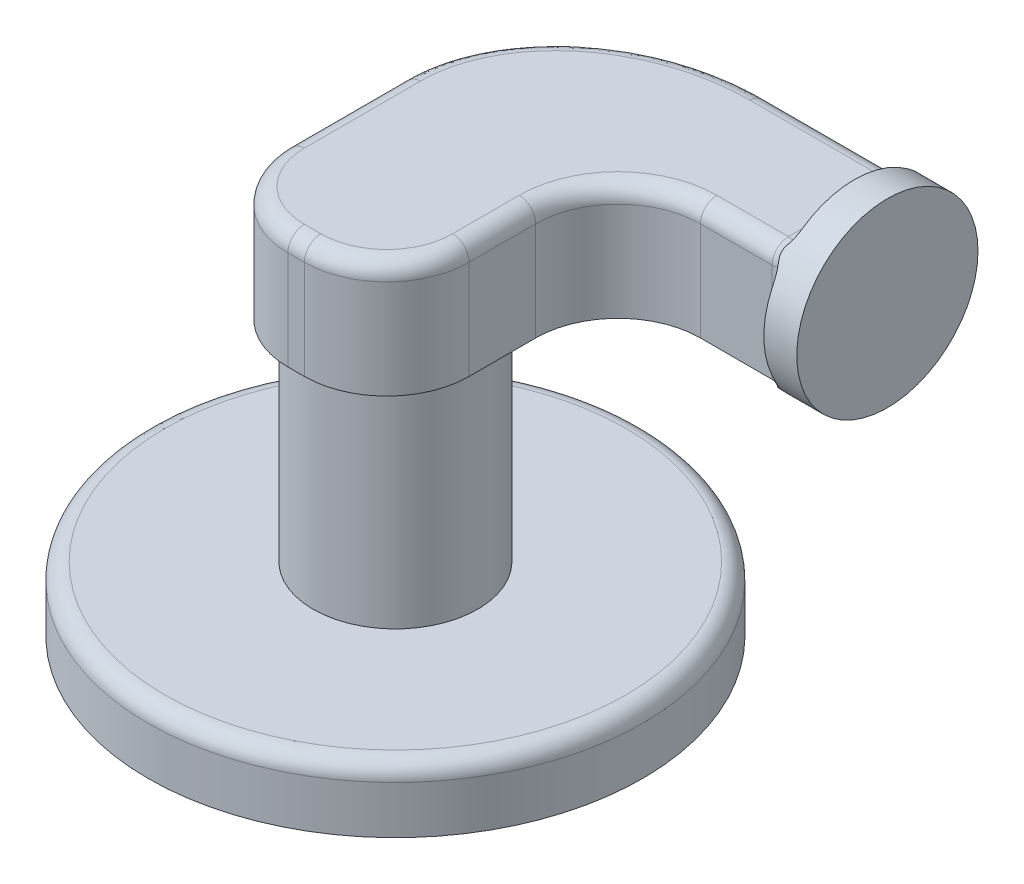
SolidWorks part; units mm, degrees
material "AISI 1020"
ref_plane "Front Plane" through (0, 0, 0) normal (0, 0, 1) x (1, 0, 0)
ref_plane "Top Plane" through (0, 0, 0) normal (0, 1, 0) x (1, 0, 0)
ref_plane "Right Plane" through (0, 0, 0) normal (1, 0, 0) x (0, 0, -1)
sketch "Sketch1" plane through (0, 0, 0) normal (0, 1, 0) x (1, 0, 0)
  circle A0 centre (0, 0) radius 15
  dimension "D1" = 30
extrude "Boss-Extrude1" add sketch "Sketch1" along normal blind 3.9
sketch "Sketch2" plane through (0, 3.9, 0) normal (0, 1, 0) x (1, 0, 0)
  circle A0 centre (0, 0) radius 5
  dimension "D1" = 10
extrude "Boss-Extrude2" add sketch "Sketch2" along normal blind 13
sketch "Sketch3" plane through (0, 16.9, 0) normal (0, 1, 0) x (1, 0, 0)
  line L0 (-5.5, -6.0256) -> (5.5, -6.0256)
  line L1 (5.5, -6.0256) -> (5.5, 8.0146)
  line L2 (5.5, 8.0146) -> (15.8436, 8.0146)
  line L3 (15.8436, 8.0146) -> (15.8436, 16.0146)
  line L4 (15.8436, 16.0146) -> (-5.5, 16.0146)
  line L5 (-5.5, 16.0146) -> (-5.5, -6.0256)
  point P2 (0, -6.0256)
  dimension "D1" = 11
  dimension "D2" = 8
extrude "Boss-Extrude3" add sketch "Sketch3" along normal blind 7
fillet "Fillet1" radius 5 3 edges at (5.5, 20.4, -8.0146) (5.5, 20.4, 6.0256) (-5.5, 20.4, 6.0256)
fillet "Fillet2" radius 12 1 edges at (-5.5, 20.4, -16.0146) second distance 10 first distance on face at (5.1718, 20.4, -16.0146)
sketch "Sketch4" plane through (15.8436, 0, 0) normal (1, 0, 0) x (0, 0, -1)
  line L0 (8.0146, 20.4) -> (16.0146, 20.4) construction
  line L1 (8.0146, 16.9) -> (16.0146, 16.9) construction
  line L2 (8.0146, 16.9) -> (8.0146, 23.9) construction
  line L3 (8.0146, 23.9) -> (16.0146, 23.9) construction
  line L4 (16.0146, 16.9) -> (16.0146, 23.9) construction
  line L5 (12.0146, 23.9) -> (12.0146, 16.9) construction
  circle A0 centre (12.0146, 20.4) radius 5.5
  dimension "D1" = 11
extrude "Boss-Extrude4" add sketch "Sketch4" along normal blind 2
fillet "Fillet3" radius 1 4 edges at (15.8436, 20.4, -16.0146) (15.8436, 16.9, -12.0146) (15.8436, 20.4, -8.0146) (15.8436, 23.9, -12.0146)
fillet "Fillet4" radius 1 1 edges at (0, 3.9, 15)
fillet "Fillet5" radius 1 11 edges at (15.0996, 23.9333, -16.0479) (15.0996, 23.9333, -7.9813) (6.9645, 23.9, -6.5502) (5.5, 23.9, -0.9945) (4.0355, 23.9, 4.5611) (0, 23.9, 6.0256) (-4.0355, 23.9, 4.5611) (12.6718, 23.9, -8.0146)
